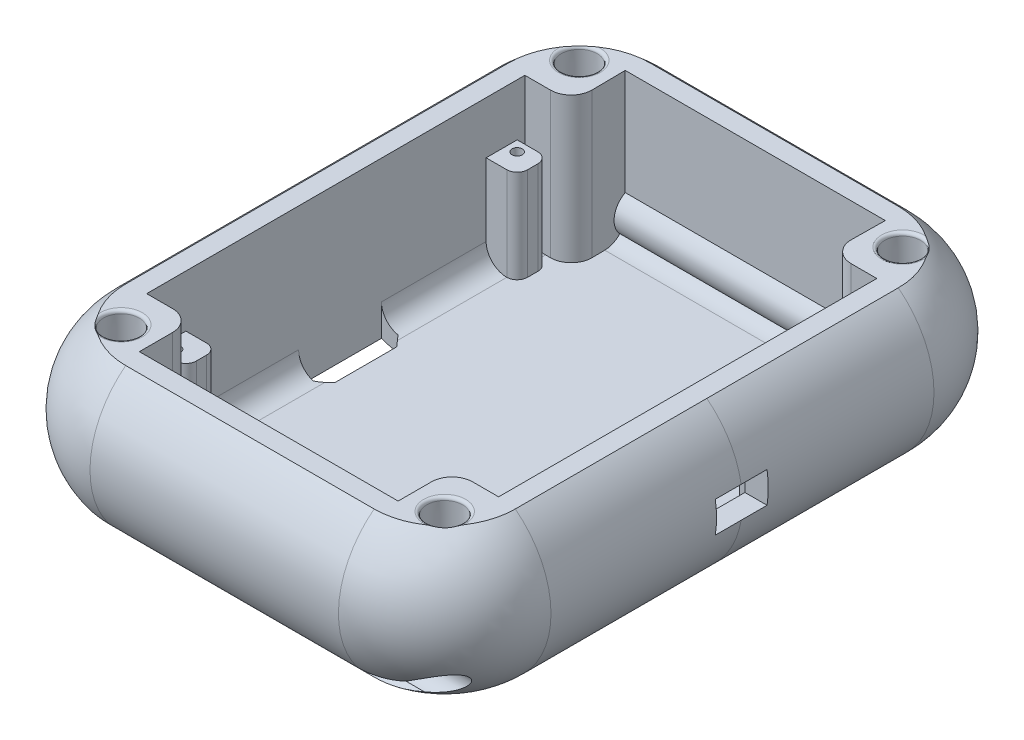
SolidWorks part; units mm, degrees
ref_plane "Front Plane" through (0, 0, 0) normal (0, 0, 1) x (1, 0, 0)
ref_plane "Top Plane" through (0, 0, 0) normal (0, 1, 0) x (1, 0, 0)
ref_plane "Right Plane" through (0, 0, 0) normal (1, 0, 0) x (0, 0, -1)
sketch "Sketch3" plane through (0, 0, 0) normal (0, 1, 0) x (1, 0, 0)
  line L1 (12, 22.5) -> (-12, 22.5)
  line L2 (16, 18.5) -> (16, -18.5)
  line L3 (12, -22.5) -> (-12, -22.5)
  line L4 (-16, 18.5) -> (-16, -18.5)
  line L5 (16, 22.5) -> (-16, -22.5) construction
  line L6 (16, -22.5) -> (-16, 22.5) construction
  arc A0 (-12, 22.5) -> (-16, 18.5) centre (-12, 18.5) ccw
  arc A1 (16, -18.5) -> (12, -22.5) centre (12, -18.5) cw
  arc A2 (12, 22.5) -> (16, 18.5) centre (12, 18.5) cw
  arc A3 (-12, -22.5) -> (-16, -18.5) centre (-12, -18.5) cw
  point P0 (0, 0)
  dimension "D3" = 4
  dimension "D1" = 32
  dimension "D2" = 45
extrude "Boss-Extrude1" add sketch "Sketch3" along normal mid plane 17
sketch "Sketch4" plane through (0, 0, 0) normal (0, 1, 0) x (1, 0, 0)
  line L1 (12, 22.5) -> (-12, 22.5)
  line L2 (16, 18.5) -> (16, -18.5)
  line L3 (12, -22.5) -> (-12, -22.5)
  line L4 (-16, 18.5) -> (-16, -18.5)
  line L5 (16, 22.5) -> (-16, -22.5) construction
  line L6 (16, -22.5) -> (-16, 22.5) construction
  arc A0 (-12, 22.5) -> (-16, 18.5) centre (-12, 18.5) ccw
  arc A1 (16, -18.5) -> (12, -22.5) centre (12, -18.5) cw
  arc A2 (12, 22.5) -> (16, 18.5) centre (12, 18.5) cw
  arc A3 (-12, -22.5) -> (-16, -18.5) centre (-12, -18.5) cw
  point P0 (0, 0)
  dimension "D3" = 4
  dimension "D1" = 32
  dimension "D2" = 45
sketch "Sketch5" plane through (0, 0, 0) normal (0, 0, 1) x (1, 0, 0)
  line L0 (16, 8.5) -> (16, -8.5)
  arc A0 (16, 8.5) -> (16, -8.5) centre (13.3686, 0) cw
sweep "Sweep1" add profiles "Sketch5" path "Sketch4"
fillet "Fillet1" radius 7 18 edges at (-14.8284, -8.5, -21.3284) (0, -8.5, -22.5) (14.8284, -8.5, -21.3284) (16, -8.5, -9.25) (16, -8.5, 9.25) (14.8284, -8.5, 21.3284) (0, -8.5, 22.5) (-14.8284, -8.5, 21.3284) (-14.8284, 8.5, -21.3284) (0, 8.5, -22.5) (14.8284, 8.5, -21.3284) (16, 8.5, -9.25) (16, 8.5, 9.25) (14.8284, 8.5, 21.3284) (0, 8.5, 22.5) (-14.8284, 8.5, 21.3284) (-16, -8.5, 0) (-16, 8.5, 0)
sketch "Sketch6" plane through (0, 0, 0) normal (0, 0, 1) x (1, 0, 0)
  line L0 (-18.8205, 7.0321) -> (18.8205, 7.0321)
  line L1 (18.8205, 7.0321) -> (18.8205, 10.7707)
  line L2 (18.8205, 10.7707) -> (-18.8205, 10.7707)
  line L3 (-18.8205, 10.7707) -> (-18.8205, 7.0321)
extrude "Cut-Extrude1" cut sketch "Sketch6" against normal through all and the other way through all
sketch "Sketch7" plane through (0, 7.0321, 0) normal (0, 1, 0) x (1, 0, 0)
  line L1 (13, 23.5) -> (-13, 23.5)
  line L2 (17, 19.5) -> (17, -19.5)
  line L3 (13, -23.5) -> (-13, -23.5)
  line L4 (-17, 19.5) -> (-17, -19.5)
  line L5 (17, 23.5) -> (-17, -23.5) construction
  line L6 (17, -23.5) -> (-17, 23.5) construction
  arc A0 (-13, 23.5) -> (-17, 19.5) centre (-13, 19.5) ccw
  arc A1 (17, -19.5) -> (13, -23.5) centre (13, -19.5) cw
  arc A2 (13, 23.5) -> (17, 19.5) centre (13, 19.5) cw
  arc A3 (-13, -23.5) -> (-17, -19.5) centre (-13, -19.5) cw
  point P0 (0, 0)
  dimension "D3" = 4
  dimension "D1" = 34
  dimension "D2" = 47
extrude "Cut-Extrude2" cut sketch "Sketch7" against normal offset from surface (14.0321 mm away) 1.5 up to face at (1.6146, -8.5, 0)
sketch "Sketch8" plane through (0, -7, 0) normal (0, 1, 0) x (1, 0, 0)
  line L1 (12.5, 23) -> (-12.5, 23)
  line L2 (12.5, 23) -> (12.5, -23)
  line L3 (12.5, -23) -> (-12.5, -23)
  line L4 (-12.5, 23) -> (-12.5, -23)
  line L5 (17, 17.5) -> (-17, 17.5)
  line L6 (17, 17.5) -> (17, -17.5)
  line L7 (17, -17.5) -> (-17, -17.5)
  line L8 (-17, 17.5) -> (-17, -17.5)
  point P0 (0, 0)
  point P6 (0, 0)
  dimension "D1" = 25
  dimension "D2" = 46
  dimension "D3" = 34
  dimension "D4" = 35
fillet "Fillet4" radius 2 8 edges at (0, -7, 23.5) (17, -7, 0) (0, -7, -23.5) (-17, -7, 0) (-15.8284, -7, 22.3284) (15.8284, -7, 22.3284) (15.8284, -7, -22.3284) (-15.8284, -7, -22.3284)
sketch "Sketch9" plane through (0, 7.0321, 0) normal (0, 1, 0) x (1, 0, 0)
  line L0 (-17, 19.5) -> (-13, 19.5)
  line L1 (-13, 19.5) -> (-13, 23.5)
  line L2 (-17, -19.5) -> (-13, -19.5)
  line L3 (-13, -19.5) -> (-13, -23.5)
  line L4 (13, 23.5) -> (13, 19.5)
  line L5 (13, 19.5) -> (17, 19.5)
  line L6 (13, -23.5) -> (13, -19.5)
  line L7 (13, -19.5) -> (17, -19.5)
  arc A0 (-13, 23.5) -> (-17, 19.5) centre (-13, 19.5) ccw
  arc A1 (-17, -19.5) -> (-13, -23.5) centre (-13, -19.5) ccw
  arc A2 (13, 23.5) -> (17, 19.5) centre (13, 19.5) cw
  arc A3 (17, -19.5) -> (13, -23.5) centre (13, -19.5) cw
extrude "Boss-Extrude2" add sketch "Sketch9" against normal up to surface (14.0321 mm away) up to face at (0, -7, 0)
sketch "Sketch11" plane through (0, 7.0321, 0) normal (0, 1, 0) x (1, 0, 0)
  line L0 (-18.8205, -18.5) -> (-18.8205, 18.5) construction
  line L1 (12, -25.3205) -> (-12, -25.3205) construction
  line L2 (18.8205, 0) -> (18.8205, -18.5) construction
  line L3 (-12, 25.3205) -> (12, 25.3205) construction
  line L4 (18.8205, 18.5) -> (18.8205, 0) construction
  circle A0 centre (-15.6205, -22.1205) radius 1.725
  circle A1 centre (15.6205, -22.1205) radius 1.725
  circle A4 centre (-15.6205, 22.1205) radius 1.725
  circle A5 centre (15.6205, 22.1205) radius 1.725
  dimension "D1" = 3.45
  dimension "D2" = 3.45
  dimension "D3" = 3.45
  dimension "D4" = 3.45
  dimension "D12" = 3.2
  dimension "D5" = 3.2
  dimension "D6" = 3.2
  dimension "D7" = 3.2
  dimension "D8" = 3.2
  dimension "D9" = 3.2
  dimension "D10" = 3.2
  dimension "D11" = 3.2
extrude "Cut-Extrude3" cut sketch "Sketch11" against normal blind 9 draft 1 draft outward yes
sketch "Sketch13" plane through (0, -7, 0) normal (0, 1, 0) x (1, 0, 0)
  line L1 (-17, -17.5) -> (-14, -17.5)
  line L2 (-17, -17.5) -> (-17, -14.5)
  line L3 (-17, -14.5) -> (-14, -14.5)
  line L4 (-14, -17.5) -> (-14, -14.5)
  line L5 (-17, 17.5) -> (-14, 17.5)
  line L6 (-17, 17.5) -> (-17, 14.5)
  line L7 (-17, 14.5) -> (-14, 14.5)
  line L8 (-14, 17.5) -> (-14, 14.5)
  line L9 (17, 17.5) -> (14, 17.5)
  line L10 (17, 17.5) -> (17, 14.5)
  line L11 (17, 14.5) -> (14, 14.5)
  line L12 (14, 17.5) -> (14, 14.5)
  line L13 (17, -17.5) -> (14, -17.5)
  line L14 (17, -17.5) -> (17, -14.5)
  line L15 (17, -14.5) -> (14, -14.5)
  line L16 (14, -17.5) -> (14, -14.5)
  dimension "D1" = 3
  dimension "D2" = 3
  dimension "D3" = 3
  dimension "D4" = 3
  dimension "D5" = 3
  dimension "D6" = 3
  dimension "D7" = 3
  dimension "D8" = 3
extrude "Boss-Extrude3" add sketch "Sketch13" along normal blind 9
sketch "Sketch14" plane through (0, 2, 0) normal (0, 1, 0) x (1, 0, 0)
  line L0 (17, 17.5) -> (-17, 17.5) construction
  line L1 (-17, 17.5) -> (-17, -17.5) construction
  line L2 (17, 17.5) -> (17, -17.5) construction
  line L3 (17, -17.5) -> (-17, -17.5) construction
  circle A0 centre (-16, 16.5) radius 0.5
  circle A1 centre (-16, -16.5) radius 0.5
  circle A2 centre (16, -16.5) radius 0.5
  circle A3 centre (16, 16.5) radius 0.5
  dimension "D1" = 1
  dimension "D4" = 1
  dimension "D5" = 1
  dimension "D6" = 1
  dimension "D2" = 1
  dimension "D3" = 1
  dimension "D7" = 1
  dimension "D8" = 1
  dimension "D9" = 1
  dimension "D10" = 1
  dimension "D11" = 1
  dimension "D12" = 1
extrude "Cut-Extrude4" cut sketch "Sketch14" against normal blind 7
sketch "Sketch28" plane through (0, -7, 0) normal (0, 1, 0) x (1, 0, 0)
  line L12 (-17, 4.3878) -> (-17, -3.6122)
  line L13 (-17, -14.5) -> (-17, 14.5) construction
  line L14 (-17, -3.6122) -> (-15.6067, -3.6122)
  line L15 (-15.6067, -3.6122) -> (-14.5, -2.6393)
  line L16 (-14.5, -2.6393) -> (-14.5, 3.3607)
  line L17 (-17, 4.3878) -> (-15.4004, 4.3878)
  line L18 (-14.5, 3.3607) -> (-15.4004, 4.3878)
  dimension "D5" = 6
  dimension "D6" = 8
  dimension "D7" = 2.5
extrude "Cut-Extrude9" cut sketch "Sketch28" against normal through all and the other way blind 3
sketch "Sketch37" plane through (0, 0, 0) normal (1, 0, 0) x (0, 0, -1)
  line L0 (0, 12.3992) -> (0, -23.3115)
  circle A0 centre (24.8584, -5.035) radius 1.5
  circle A1 centre (-24.8584, -5.035) radius 1.5
  dimension "D1" = 3
extrude "Cut-Extrude14" cut sketch "Sketch37" against normal through all and the other way through all contours A1 | A0
fillet "Fillet20" radius 1 12 edges at (14, -2.5, -14.5) (14, -2.5, -17.5) (14, -2.5, 17.5) (14, -2.5, 14.5) (-14, -2.5, -14.5) (-14, -2.5, -17.5) (-14, -2.5, 17.5) (-14, -2.5, 14.5) (13, 0.0161, 19.5) (13, 0.0161, -19.5) (-13, 0.0161, 19.5) (-13, 0.0161, -19.5)
sketch "Sketch38" plane through (0, 0, 0) normal (1, 0, 0) x (0, 0, -1)
  line L0 (0, 36.7864) -> (0, -15.0217)
  line L1 (26.3423, -4.8155) -> (27.2577, -5.7309)
  line L2 (27.2577, -5.7309) -> (25.668, -7.3206)
  line L3 (25.668, -7.3206) -> (24.6389, -6.5188)
  line L4 (24.6389, -6.5188) -> (26.3423, -4.8155)
  line L5 (-25.668, -7.3206) -> (-24.6389, -6.5188)
  line L6 (-27.2577, -5.7309) -> (-25.668, -7.3206)
  line L7 (-26.3423, -4.8155) -> (-27.2577, -5.7309)
  line L8 (-24.6389, -6.5188) -> (-26.3423, -4.8155)
  circle A0 centre (24.8584, -5.035) radius 1.5 construction
  point P4 (0, 10.8824)
extrude "Cut-Extrude15" cut sketch "Sketch38" against normal through all and the other way through all contours L4 L3 L2 L1 | L5 L8 L7 L6 region at (0, -6.0915, -25.9712) region at (0, -6.0915, 25.9712)
sketch "Sketch39" plane through (-13, 0, 0) normal (1, 0, 0) x (0, 0, -1)
  line L4 (23.5, -4.3988) -> (23.5, -3.1934)
  line L5 (23.5, -4.3988) -> (23.5, 7.0321) construction
  line L7 (0, 12.0331) -> (0, -15.5542) construction
  line L8 (-23.5, -4.3988) -> (-23.5, -3.1934)
  arc A0 (23.5, -4.3988) -> (23.4347, -5.507) centre (24.8584, -5.035) ccw
  arc A4 (21.5, -7) -> (23.4347, -5.507) centre (21.5, -5) ccw construction
  arc A5 (23.4347, -5.507) -> (22.969, -6.3573) centre (21.5, -5) cw
  arc A6 (23.5, -3.1934) -> (22.969, -6.3573) centre (24.4057, -4.9719) ccw
  arc A7 (-23.5, -4.3988) -> (-23.4347, -5.507) centre (-24.8584, -5.035) cw
  arc A8 (-23.4347, -5.507) -> (-22.969, -6.3573) centre (-21.5, -5) ccw
  arc A9 (-23.5, -3.1934) -> (-22.969, -6.3573) centre (-24.4057, -4.9719) cw
extrude "Boss-Extrude4" add sketch "Sketch39" along normal up to surface (26 mm away) up to face at (13, -1.6942, -22.1805)
sketch "Sketch40" plane through (0, 7.0321, 0) normal (0, 1, 0) x (1, 0, 0)
  line L0 (-17, 19.5) -> (-14, 19.5)
  line L1 (-13, 20.5) -> (-13, 23.5)
  line L2 (-13, 23.5) -> (-12.5624, 23.5)
  line L3 (13, 23.5) -> (-13, 23.5) construction
  line L4 (-12.5624, 23.5) -> (-12.5, 18.2433)
  line L5 (-12.5, 23) -> (-12.5, -23) construction
  line L6 (-12.5, 18.2433) -> (-17, 18.2433)
  line L7 (-17, 17.5) -> (-17, 19.5) construction
  line L8 (-17, 18.2433) -> (-17, 19.5)
  line L9 (-17, -19.5) -> (-14, -19.5)
  line L10 (-13, -20.5) -> (-13, -23.5)
  line L11 (-13, -23.5) -> (-12.5, -23.5)
  line L12 (13, -23.5) -> (-13, -23.5) construction
  line L13 (-12.5, -23.5) -> (-12.5, -18.2929)
  line L14 (-12.5, -18.2929) -> (-17, -18.2929)
  line L15 (-17, 19.5) -> (-17, -19.5) construction
  line L16 (-17, -18.2929) -> (-17, -19.5)
  line L17 (0, 31.3082) -> (0, -41.0309) construction
  line L18 (12.5, 18.2433) -> (17, 18.2433)
  line L19 (12.5624, 23.5) -> (12.5, 18.2433)
  line L20 (13, 23.5) -> (12.5624, 23.5)
  line L21 (13, 20.5) -> (13, 23.5)
  line L22 (17, 19.5) -> (14, 19.5)
  line L23 (17, 18.2433) -> (17, 19.5)
  line L24 (12.5, -18.2929) -> (17, -18.2929)
  line L25 (12.5, -23.5) -> (12.5, -18.2929)
  line L26 (13, -23.5) -> (12.5, -23.5)
  line L27 (13, -20.5) -> (13, -23.5)
  line L28 (17, -19.5) -> (14, -19.5)
  line L29 (17, -18.2929) -> (17, -19.5)
  arc A0 (-14, 19.5) -> (-13, 20.5) centre (-14, 20.5) ccw
  arc A1 (-14, -19.5) -> (-13, -20.5) centre (-14, -20.5) cw
  arc A2 (14, 19.5) -> (13, 20.5) centre (14, 20.5) cw
  arc A3 (14, -19.5) -> (13, -20.5) centre (14, -20.5) ccw
extrude "Boss-Extrude5" add sketch "Sketch40" against normal up to surface (14.0321 mm away) up to face at (-1.6389, -7, -0.0437)
fillet "Fillet21" radius 2 4 edges at (12.5, 0.0161, 18.2929) (12.5, 0.0161, -18.2433) (-12.5, 0.0161, 18.2929) (-12.5, 0.0161, -18.2433)
fillet "Fillet22" radius 0.3 4 edges at (-14.4007, 7.0321, 20.9007) (-14.4007, 7.0321, -20.9007) (14.4007, 7.0321, -20.9007) (14.4007, 7.0321, 20.9007)
sketch "Sketch41" plane through (17, 0, 0) normal (-1, 0, 0) x (0, 0, 1)
  line L1 (5, 3) -> (-5, 3)
  line L2 (5, 3) -> (5, -3)
  line L3 (5, -3) -> (-5, -3)
  line L4 (-5, 3) -> (-5, -3)
  line L5 (5, 3) -> (-5, -3) construction
  line L6 (5, -3) -> (-5, 3) construction
  point P0 (0, 0)
  dimension "D1" = 10
  dimension "D2" = 6
extrude "Cut-Extrude16" cut sketch "Sketch41" against normal blind 3
sketch "Sketch42" plane through (20, 0, 0) normal (-1, 0, 0) x (0, 0, 1)
  line L1 (2.5, 1.5) -> (-2.5, 1.5)
  line L2 (2.5, 1.5) -> (2.5, -1.5)
  line L3 (2.5, -1.5) -> (-2.5, -1.5)
  line L4 (-2.5, 1.5) -> (-2.5, -1.5)
  line L5 (2.5, 1.5) -> (-2.5, -1.5) construction
  line L6 (2.5, -1.5) -> (-2.5, 1.5) construction
  point P0 (0, 0)
  dimension "D1" = 3
  dimension "D2" = 5
extrude "Cut-Extrude17" cut sketch "Sketch42" against normal blind 2.5
sketch "Sketch48" plane through (17, 0, 0) normal (-1, 0, 0) x (0, 0, 1)
  line L1 (-5, -3) -> (5, -3)
  line L2 (-5, -3) -> (-5, -5.5)
  line L3 (-5, -5.5) -> (5, -5.5)
  line L4 (5, -3) -> (5, -5.5)
  dimension "D1" = 2.5
  dimension "D2" = 10
extrude "Cut-Extrude18" cut sketch "Sketch48" against normal up to surface (3 mm away) up to face at (20, 0, 0)
